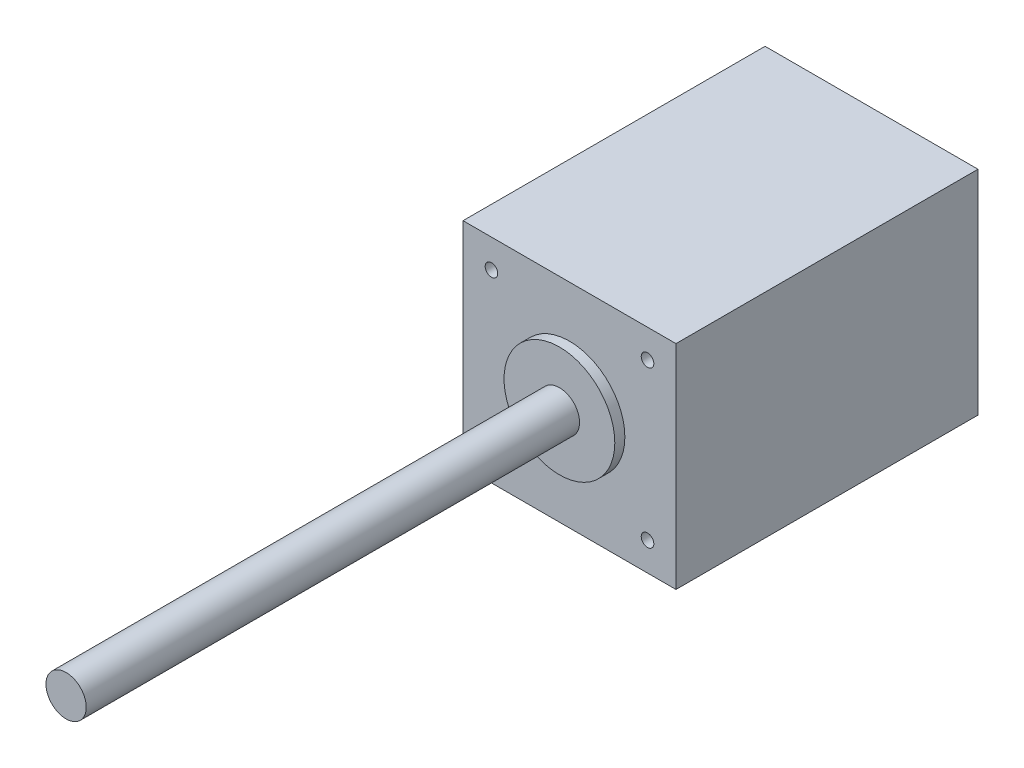
SolidWorks part; units mm, degrees
ref_plane "前视基准面" through (0, 0, 0) normal (0, 0, 1) x (1, 0, 0)
ref_plane "上视基准面" through (0, 0, 0) normal (0, 1, 0) x (1, 0, 0)
ref_plane "右视基准面" through (0, 0, 0) normal (1, 0, 0) x (0, 0, -1)
other "Configuration Table"
sketch "草图1" plane through (0, 0, 0) normal (0, 0, 1) x (1, 0, 0)
  line L1 (21.15, -21.15) -> (-21.15, -21.15)
  line L2 (21.15, -21.15) -> (21.15, 21.15)
  line L3 (21.15, 21.15) -> (-21.15, 21.15)
  line L4 (-21.15, -21.15) -> (-21.15, 21.15)
  line L5 (21.15, -21.15) -> (-21.15, 21.15) construction
  line L6 (21.15, 21.15) -> (-21.15, -21.15) construction
  point P0 (0, 0)
  dimension "D1" = 42.3
  dimension "D2" = 42.3
extrude "凸台-拉伸1" add sketch "草图1" along normal blind 60
sketch "草图2" plane through (0, 0, 60) normal (0, 0, 1) x (1, 0, 0)
  circle A0 centre (0, 0) radius 11
  dimension "D1" = 22
extrude "凸台-拉伸2" add sketch "草图2" along normal blind 2
sketch "草图3" plane through (0, 0, 62) normal (0, 0, 1) x (1, 0, 0)
  circle A0 centre (0, 0) radius 4
extrude "凸台-拉伸3" add sketch "草图3" along normal blind 98
sketch "草图4" plane through (0, 0, 60) normal (0, 0, 1) x (1, 0, 0)
  line L0 (-21.15, 21.15) -> (-21.15, -21.15) construction
  line L2 (21.15, 21.15) -> (-21.15, 21.15) construction
  line L3 (-21.15, -21.15) -> (21.15, -21.15) construction
  point P0 (-15.5, 15.5)
  point P1 (15.5, 15.5)
  point P2 (-15.5, -15.5)
  point P3 (15.5, -15.5)
  dimension "D1" = 31
  dimension "D2" = 5.65
  dimension "D3" = 5.65
  dimension "D4" = 5.65
  dimension "D5" = 5.65
  dimension "D6" = 5.65
  dimension "D7" = 31
  dimension "D8" = 5.65
sketch "草图5" plane through (0, 0, 60) normal (0, 0, 1) x (1, 0, 0)
  point P0 (-15.5, 15.5)
  point P3 (15.5, 15.5)
  point P6 (15.5, -15.5)
  point P9 (-15.5, -15.5)
hole_wizard "M3 螺纹孔1" positions "草图5" profile "草图6" tap size "M3" standard "GB" end condition through all
sketch "草图6" plane through (-15.5, 15.5, 60) normal (1, 0, 0) x (0, -1, 0)
  line L0 (0, 0) -> (0, 60)
  line L1 (0, 60) -> (1.25, 60)
  line L2 (1.25, 60) -> (1.25, 0)
  line L5 (1.25, 0) -> (0, 0)
  line L11 (0, -6.35) -> (0, 107.95) construction
  dimension "通孔螺纹孔钻头直径" = 2.5
  dimension "通孔螺纹孔钻头深度" = 60
cosmetic thread "孔螺蚊线1" parameters "D2"=3
cosmetic thread "孔螺蚊线2" parameters "D2"=3
cosmetic thread "孔螺蚊线3" parameters "D2"=3
cosmetic thread "孔螺蚊线4" parameters "D2"=3
